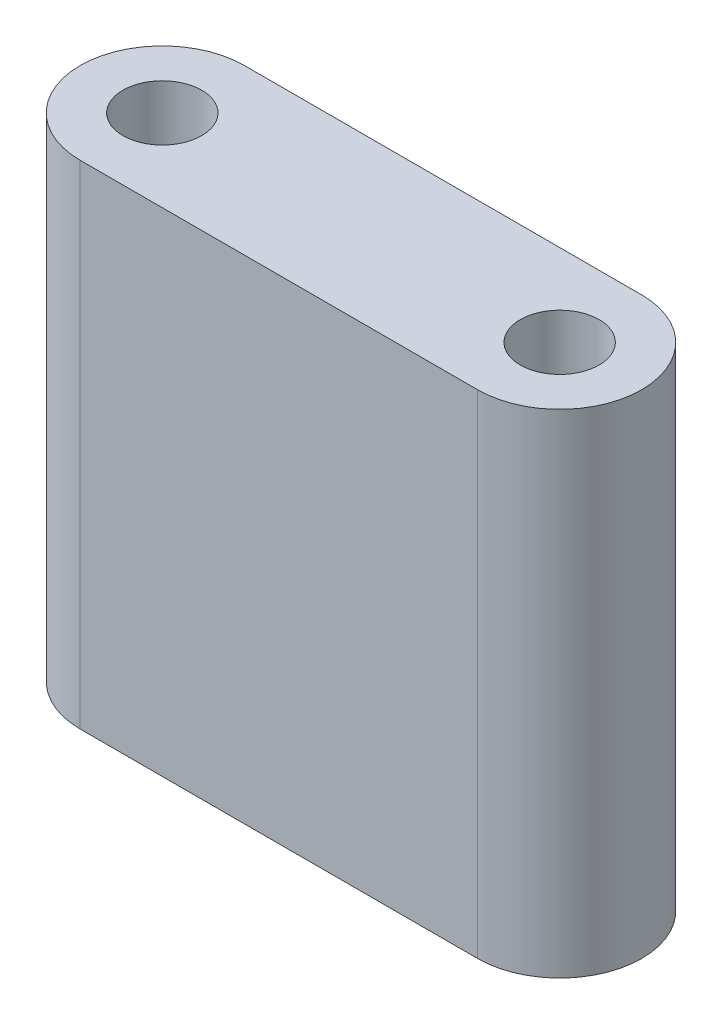
SolidWorks part; units mm, degrees
ref_plane "前视基准面" through (0, 0, 0) normal (0, 0, 1) x (1, 0, 0)
ref_plane "上视基准面" through (0, 0, 0) normal (0, 1, 0) x (1, 0, 0)
ref_plane "右视基准面" through (0, 0, 0) normal (1, 0, 0) x (0, 0, -1)
other "Configuration Table"
sketch "草图1" plane through (0, 0, 0) normal (0, 1, 0) x (1, 0, 0)
  line L0 (-6.05, 0) -> (6.05, 0) construction
  line L1 (-6.05, 0) -> (6.05, 0) construction
  line L2 (-6.05, 2.5) -> (6.05, 2.5)
  line L3 (-6.05, -2.5) -> (6.05, -2.5)
  circle A0 centre (6.05, 0) radius 1.2
  circle A1 centre (-6.05, 0) radius 1.2
  arc A2 (-6.05, 2.5) -> (-6.05, -2.5) centre (-6.05, 0) ccw
  arc A3 (6.05, -2.5) -> (6.05, 2.5) centre (6.05, 0) ccw
  circle A4 centre (-6.05, 0) radius 2.5
  point P4 (0, 0)
  point P8 (0, 0)
  dimension "D2" = 2.4
  dimension "D3" = 2.5
  dimension "D1" = 12.1
extrude "凸台-拉伸1" add sketch "草图1" along normal blind 15 contours A4 L3 A3 L2 A0 | A2 A4 A1 region at (-4.3322, 0, -1.7178) region at (1.6332, 0, 0)
extrude "凸台-拉伸2" add sketch "草图1<3>" along normal blind 15 contours A2 A4 A1 region at (-4.3322, 0, -1.7178)
sketch "草图1<3>" plane through (0, 0, 0) normal (0, 1, 0) x (1, 0, 0) same geometry as "草图1"
chamfer "倒角1" [suppressed] distance 2 angle 45
